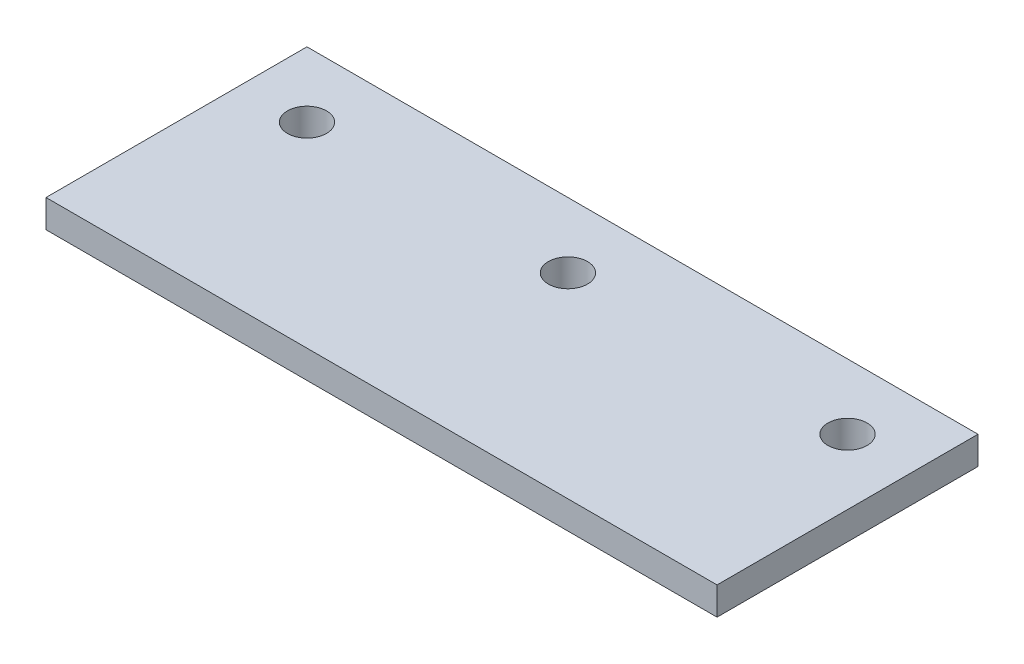
SolidWorks part; units mm, degrees
ref_plane "Front Plane" through (0, 0, 0) normal (0, 0, 1) x (1, 0, 0)
ref_plane "Top Plane" through (0, 0, 0) normal (0, 1, 0) x (1, 0, 0)
ref_plane "Right Plane" through (0, 0, 0) normal (1, 0, 0) x (0, 0, -1)
sketch "Sketch1" plane through (0, 0, 0) normal (0, 1, 0) x (1, 0, 0)
  line L0 (0, 0) -> (72, 0)
  line L1 (72, 0) -> (72, -28)
  line L2 (72, -28) -> (0, -28)
  line L3 (0, -28) -> (0, 0)
  circle A0 centre (7, -7) radius 2.1
  circle A1 centre (35, -7) radius 2.1
  circle A2 centre (65, -7) radius 2.1
  dimension "D3" = 4.2
  dimension "D4" = 7
  dimension "D1" = 72
  dimension "D2" = 28
  dimension "D5" = 28
  dimension "D6" = 7
  dimension "D7" = 7
extrude "Boss-Extrude1" add sketch "Sketch1" along normal blind 3
